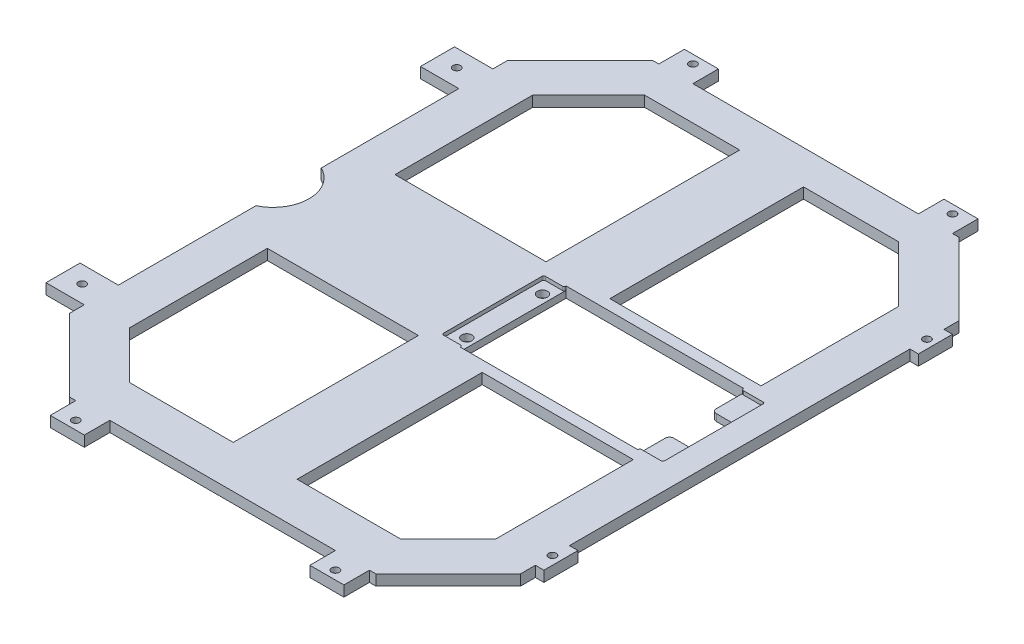
SolidWorks part; units mm, degrees
ref_plane "Front Plane" through (0, 0, 0) normal (0, 0, 1) x (1, 0, 0)
ref_plane "Top Plane" through (0, 0, 0) normal (0, 1, 0) x (1, 0, 0)
ref_plane "Right Plane" through (0, 0, 0) normal (1, 0, 0) x (0, 0, -1)
sketch "Sketch1" plane through (0, 0, 0) normal (0, 1, 0) x (1, 0, 0)
  line L1 (0, 0) -> (106, 0)
  line L2 (0, 0) -> (0, -137)
  line L3 (0, -137) -> (106, -137)
  line L4 (106, 0) -> (106, -137)
  line L5 (0, 0) -> (106, -137) construction
  line L6 (0, -137) -> (106, 0) construction
  point P4 (53, -68.5)
  dimension "D1" = 137
  dimension "D2" = 106
extrude "Boss-Extrude1" add sketch "Sketch1" along normal blind 2.5
sketch "Sketch2" plane through (0, 2.5, 0) normal (0, 1, 0) x (1, 0, 0)
  line L0 (0, -120) -> (17, -137)
  line L1 (0, 0) -> (0, -137) construction
  line L2 (0, -137) -> (106, -137) construction
  line L3 (17, -137) -> (0, -137)
  line L4 (0, -137) -> (0, -120)
  line L5 (89, -137) -> (106, -120)
  line L6 (106, -137) -> (106, 0) construction
  line L7 (106, -120) -> (106, -137)
  line L8 (106, -137) -> (89, -137)
  line L9 (89, 0) -> (106, -17)
  line L10 (106, 0) -> (0, 0) construction
  line L11 (106, -17) -> (106, 0)
  line L12 (106, 0) -> (89, 0)
  line L13 (0, 0) -> (17, 0)
  line L14 (17, 0) -> (0, -17)
  line L15 (0, -17) -> (0, 0)
  line L16 (10, -21.1421) -> (23.1421, -8)
  line L17 (23.1421, -8) -> (45.5, -8)
  line L18 (82.8579, -8) -> (96, -21.1421)
  line L19 (96, -21.1421) -> (96, -53.5)
  line L20 (96, -115.8579) -> (84.8579, -127)
  line L21 (84.8579, -127) -> (60.5, -127)
  line L22 (21.1421, -127) -> (10, -115.8579)
  line L23 (10, -115.8579) -> (10, -83.5)
  line L24 (96, -83.5) -> (96, -53.5) construction
  line L25 (10, -83.5) -> (45.5, -83.5)
  line L27 (10, -53.5) -> (45.5, -53.5)
  line L29 (0, -68.5) -> (106, -68.5) construction
  line L30 (45.5, -127) -> (21.1421, -127)
  line L31 (96, -83.5) -> (96, -115.8579)
  line L33 (10, -53.5) -> (10, -21.1421)
  line L34 (45.5, -127) -> (45.5, -83.5)
  line L36 (60.5, -127) -> (60.5, -83.5)
  line L37 (60.5, -53.5) -> (96, -53.5)
  line L38 (60.5, -8) -> (82.8579, -8)
  line L40 (45.5, -53.5) -> (45.5, -8)
  line L42 (60.5, -53.5) -> (60.5, -8)
  line L43 (60.5, -83.5) -> (96, -83.5)
  line L44 (53, -137) -> (53, 0) construction
  line L45 (45.5, -127) -> (60.5, -127) construction
  point P38 (96, -68.5)
  point P43 (53, -127)
  line M40 (0, 0) -> (0, -137)
  line M41 (0, -137) -> (106, -137)
  line M42 (106, -137) -> (106, 0)
  line M43 (106, 0) -> (0, 0)
  dimension "D1" = 17
  dimension "D2" = 17
  dimension "D3" = 17
  dimension "D4" = 17
  dimension "D5" = 17
  dimension "D6" = 17
  dimension "D7" = 17
  dimension "D8" = 17
  dimension "D9" = 8
  dimension "D10" = 10
  dimension "D11" = 10
  dimension "D12" = 10
  dimension "D13" = 10
  dimension "D14" = 10
  dimension "D15" = 10
  dimension "D16" = 10
  dimension "D17" = 30
  dimension "D18" = 15
  dimension "D19" = 15
extrude "Cut-Extrude1" cut sketch "Sketch2" against normal through all both and the other way through all contours L43 L36 L21 L20 L31 | L5 M41 M42 | L0 M40 M41 | L30 L34 L25 L23 L22 | L27 L40 L17 L16 L33 | L42 L37 L19 L18 L38 | L9 M43 M42 | L14 M43 M40 | L4 L0 L3 | L23 L25 L34 L30 L22 region at (5.6667, 2.5, 131.3333) region at (5.6667, 2.5, 5.6667) region at (100.3333, 2.5, 131.3333) region at (100.3333, 2.5, 5.6667) region at (28.5052, 2.5, 31.7876) region at (77.4948, 2.5, 31.7876) region at (77.6622, 2.5, 104.4947) region at (28.3378, 2.5, 104.4947)
sketch "Sketch3" plane through (0, 2.5, 0) normal (0, 1, 0) x (1, 0, 0)
  line L0 (50.7756, -77.39) -> (50.7756, -59.61) construction
  line L5 (96.5, -78.0568) -> (96.5, -58.9433) construction
  line L7 (106, -120) -> (106, -17) construction
  line L8 (106, -68.5) -> (0, -68.5) construction
  line L9 (0, -17) -> (0, -120) construction
  line L10 (52.7756, -80.94) -> (94.5, -80.94)
  line L15 (94.5, -80.94) -> (94.5, -78.0568)
  line L27 (94.5, -58.9433) -> (94.5, -56.06)
  line L28 (94.5, -56.06) -> (52.7756, -56.06)
  line L29 (52.7756, -56.06) -> (52.7756, -59.61)
  line L30 (52.7756, -77.39) -> (52.7756, -80.94)
  line L34 (52.7756, -59.61) -> (52.7756, -77.39)
  line L35 (94.5, -58.9433) -> (94.5, -78.0568)
  circle A0 centre (50.7756, -77.39) radius 2
  circle A1 centre (50.7756, -59.61) radius 2
  circle A2 centre (96.5, -78.0568) radius 2
  circle A3 centre (96.5, -58.9433) radius 2
  circle A4 centre (50.7756, -77.39) radius 1.2
  circle A5 centre (50.7756, -59.61) radius 1.2
  circle A6 centre (96.5, -58.9433) radius 1.2
  circle A7 centre (96.5, -78.0568) radius 1.2
  arc A8 (50.7756, -75.39) -> (52.7756, -77.39) centre (50.7756, -77.39) cw
  arc A9 (52.7756, -59.61) -> (48.7756, -59.61) centre (50.7756, -59.61) cw
  arc A10 (94.5, -58.9433) -> (96.5, -60.9433) centre (96.5, -58.9433) ccw
  arc A11 (94.5, -78.0568) -> (96.5, -76.0568) centre (96.5, -78.0568) cw
  point P10 (50.7756, -68.5)
  point P11 (96.5, -68.5)
  point P24 (77.2368, -68.8611)
  point P34 (100.0995, -68.5)
  point P47 (101.1659, -76.1818)
  point P50 (100.1684, -60.8183)
  dimension "D4" = 4
  dimension "D5" = 4
  dimension "D6" = 4
  dimension "D7" = 4
  dimension "D8" = 2.4
  dimension "D9" = 2.4
  dimension "D10" = 2.4
  dimension "D11" = 2.4
  dimension "D12" = 9.5
  dimension "D1" = 19.1135
  dimension "D2" = 17.78
  dimension "D3" = 45.7244
  dimension "D15" = 3.55
  dimension "D16" = 3.55
sketch "Sketch5" plane through (0, 0, 0) normal (0, 1, 0) x (1, 0, 0)
  line L0 (0, -68.5) -> (106, -68.5) construction
  line L1 (-4.5, -112.5) -> (110.5, -112.5) construction
  line L2 (-4.5, -112.5) -> (-4.5, -24.5) construction
  line L3 (-4.5, -24.5) -> (110.5, -24.5) construction
  line L4 (110.5, -112.5) -> (110.5, -24.5) construction
  line L5 (-4.5, -112.5) -> (110.5, -24.5) construction
  line L6 (-4.5, -24.5) -> (110.5, -112.5) construction
  line L7 (22.5, 4) -> (83.5, 4) construction
  line L8 (22.5, 4) -> (22.5, -141) construction
  line L9 (22.5, -141) -> (83.5, -141) construction
  line L10 (83.5, 4) -> (83.5, -141) construction
  line L11 (22.5, 4) -> (83.5, -141) construction
  line L12 (22.5, -141) -> (83.5, 4) construction
  line L13 (0, -17) -> (0, -120) construction
  line L14 (106, -120) -> (106, -17) construction
  line L15 (53, -137) -> (53, 0) construction
  line L16 (17, -137) -> (89, -137) construction
  line L17 (89, 0) -> (17, 0) construction
  line L23 (18.5, 0) -> (26.5, 0)
  line L24 (18.5, 0) -> (18.5, 6)
  line L29 (18.5, 6) -> (26.5, 6)
  line L30 (26.5, 0) -> (26.5, 6)
  line L35 (18.5, 0) -> (26.5, 6) construction
  line L36 (18.5, 6) -> (26.5, 0) construction
  line L41 (79.5, 6) -> (87.5, 6)
  line L42 (79.5, 6) -> (79.5, 0)
  line L43 (0, -116.5) -> (-9, -116.5)
  line L44 (0, -116.5) -> (0, -108.5)
  line L45 (0, -108.5) -> (-9, -108.5)
  line L46 (-9, -116.5) -> (-9, -108.5)
  line L47 (0, -116.5) -> (-9, -108.5) construction
  line L48 (0, -108.5) -> (-9, -116.5) construction
  line L49 (0, -28.5) -> (-9, -28.5)
  line L50 (0, -28.5) -> (0, -20.5)
  line L51 (0, -20.5) -> (-9, -20.5)
  line L52 (-9, -28.5) -> (-9, -20.5)
  line L53 (0, -28.5) -> (-9, -20.5) construction
  line L54 (0, -20.5) -> (-9, -28.5) construction
  line L59 (106, -116.5) -> (108, -116.5)
  line L60 (106, -116.5) -> (106, -108.5)
  line L65 (106, -108.5) -> (108, -108.5)
  line L66 (108, -116.5) -> (108, -108.5)
  line L67 (106, -116.5) -> (108, -108.5) construction
  line L68 (106, -108.5) -> (108, -116.5) construction
  line L69 (106, -28.5) -> (108, -28.5)
  line L70 (106, -28.5) -> (106, -20.5)
  line L71 (106, -20.5) -> (108, -20.5)
  line L72 (108, -28.5) -> (108, -20.5)
  line L73 (106, -28.5) -> (108, -20.5) construction
  line L74 (106, -20.5) -> (108, -28.5) construction
  line L75 (79.5, 0) -> (87.5, 0)
  line L76 (87.5, 6) -> (87.5, 0)
  line L77 (79.5, 6) -> (87.5, 0) construction
  line L78 (79.5, 0) -> (87.5, 6) construction
  line L79 (79.5, -137) -> (87.5, -137)
  line L80 (79.5, -137) -> (79.5, -143)
  line L81 (79.5, -143) -> (87.5, -143)
  line L82 (87.5, -137) -> (87.5, -143)
  line L83 (79.5, -137) -> (87.5, -143) construction
  line L84 (79.5, -143) -> (87.5, -137) construction
  line L85 (18.5, -137) -> (26.5, -137)
  line L86 (18.5, -137) -> (18.5, -143)
  line L87 (18.5, -143) -> (26.5, -143)
  line L88 (26.5, -137) -> (26.5, -143)
  line L89 (18.5, -137) -> (26.5, -143) construction
  line L90 (18.5, -143) -> (26.5, -137) construction
  circle A0 centre (-4.5, -112.5) radius 0.9
  circle A1 centre (-4.5, -24.5) radius 0.9
  circle A2 centre (22.5, 4) radius 0.9
  circle A3 centre (83.5, 4) radius 0.9
  circle A6 centre (83.5, -141) radius 0.9
  circle A7 centre (22.5, -141) radius 0.9
  circle A8 centre (106, -112.5) radius 0.9
  circle A9 centre (106, -24.5) radius 0.9
  point P4 (53, -68.5)
  point P9 (53, -68.5)
  point P27 (22.5, 3)
  point P28 (22.5, -141)
  point P29 (22.5, 6)
  point P32 (83.5, -141)
  point P35 (83.5, 3)
  point P36 (83.5, 6)
  point P37 (83.5, 4)
  point P42 (22.5, 4)
  point P48 (-4.5, -112.5)
  point P52 (-4.5, -24.5)
  point P57 (107, -112.5)
  point P62 (107, -24.5)
  point P70 (83.5, -140)
  point P73 (83.5, -143)
  point P78 (22.5, -140)
  dimension "D13" = 1.8
  dimension "D14" = 1.8
  dimension "D15" = 1.8
  dimension "D16" = 1.8
  dimension "D17" = 8
  dimension "D18" = 2
  dimension "D19" = 1.8
  dimension "D20" = 1.8
  dimension "D21" = 1.8
  dimension "D22" = 1.8
  dimension "D1" = 61
  dimension "D2" = 145
  dimension "D3" = 88
  dimension "D4" = 115
  dimension "D5" = 8
  dimension "D6" = 8
  dimension "D7" = 6
  dimension "D8" = 6
  dimension "D9" = 8
  dimension "D10" = 8
  dimension "D11" = 2
  dimension "D12" = 8
  dimension "D23" = 8
  dimension "D24" = 6
  dimension "D25" = 8
  dimension "D26" = 6
extrude "Boss-Extrude4" add sketch "Sketch5" along normal up to surface (2.5 mm away) contours A8 L60 L59 L66 L65 | A6 | L30 A7 | L46 L43 L44 L45 A0 | L52 L49 L50 L51 A1 | L79 L82 L81 L80 A2 | A3 | A9 L70 L69 L72 L71 region at (22.5, 0, -2.944) region at (83.5, 0, -2.944) region at (-4.5, 0, 116.3796) region at (-4.5, 0, 28.3796) region at (107.0534, 0, 112.5) region at (107.0534, 0, 24.5) region at (83.5, 0, 139.944) region at (22.5, 0, 139.944) up to face at (26.8284, 2.5, 28.8284)
ref_plane "Plane1" through (53, 0, 0) normal (-1, 0, 0) x (0, 0, 1)
ref_plane "Plane2" through (0, 0, 68.5) normal (0, 0, 1) x (1, 0, 0)
extrude "Cut-Extrude4" cut sketch "Sketch3" against normal through all both and the other way through all contours L35 L27 L28 L29 L34 L30 L10 L15 | A5 | A4
sketch "Sketch8" plane through (0, 2.5, 0) normal (0, 1, 0) x (1, 0, 0)
  line L0 (106, -25.4) -> (106, -23.6) construction
  line L1 (106, -113.4) -> (106, -111.6) construction
  circle A0 centre (106, -24.5) radius 0.9
  circle A1 centre (106, -112.5) radius 0.9
extrude "Cut-Extrude6" cut sketch "Sketch8" against normal through all both and the other way through all
sketch "Sketch9" plane through (0, 2.5, 0) normal (0, 1, 0) x (1, 0, 0)
  line L0 (106, -68.5) -> (0, -68.5) construction
  line L1 (47.9756, -56.525) -> (99.9256, -56.525)
  line L2 (47.9756, -56.525) -> (47.9756, -80.475)
  line L3 (47.9756, -80.475) -> (99.9256, -80.475)
  line L4 (99.9256, -56.525) -> (99.9256, -80.475)
  line L5 (47.9756, -56.525) -> (99.9256, -80.475) construction
  line L6 (47.9756, -80.475) -> (99.9256, -56.525) construction
  line L7 (106, -108.5) -> (106, -28.5) construction
  line L8 (0, -28.5) -> (0, -108.5) construction
  circle A0 centre (50.7756, -59.61) radius 1.2 construction
  point P4 (73.9506, -68.5)
  dimension "D3" = 2.8
  dimension "D1" = 51.95
  dimension "D2" = 23.95
extrude "Cut-Extrude7" cut sketch "Sketch9" against normal blind 0.89 and the other way through all
fillet "Fillet2" radius 0.4 8 edges at (94.5, 2.055, 80.475) (99.9256, 2.055, 80.475) (99.9256, 2.055, 56.525) (94.5, 2.055, 56.525) (52.7756, 2.055, 56.525) (47.9756, 2.055, 56.525) (52.7756, 2.055, 80.475) (47.9756, 2.055, 80.475)
sketch "Sketch11" plane through (0, 2.5, 0) normal (0, 1, 0) x (1, 0, 0)
  circle A0 centre (-3.6747, -68.5) radius 8.5
  dimension "D1" = 17
extrude "Cut-Extrude9" cut sketch "Sketch11" against normal through all both and the other way through all
sketch "Sketch12" plane through (0, 1.61, 0) normal (0, 1, 0) x (1, 0, 0)
  line L0 (94.5, -80.875) -> (94.5, -56.125) construction
  line L1 (94.5, -63.5) -> (99.9256, -63.5)
  line L2 (94.5, -63.5) -> (94.5, -73.5)
  line L3 (94.5, -73.5) -> (99.9256, -73.5)
  line L4 (99.9256, -63.5) -> (99.9256, -73.5)
  line L5 (94.5, -63.5) -> (99.9256, -73.5) construction
  line L6 (94.5, -73.5) -> (99.9256, -63.5) construction
  line L7 (99.9256, -56.925) -> (99.9256, -80.075) construction
  line L8 (97.2128, -56.525) -> (97.2128, -80.475) construction
  line L9 (99.5256, -56.525) -> (94.9, -56.525) construction
  line L10 (94.9, -80.475) -> (99.5256, -80.475) construction
  point P4 (97.2128, -68.5)
  point P15 (97.2128, -68.5)
  dimension "D1" = 10
extrude "Cut-Extrude10" cut sketch "Sketch12" against normal through all both and the other way through all
fillet "Fillet3" radius 1 4 edges at (94.5, 0.805, 73.5) (99.9256, 0.805, 73.5) (99.9256, 0.805, 63.5) (94.5, 0.805, 63.5)
